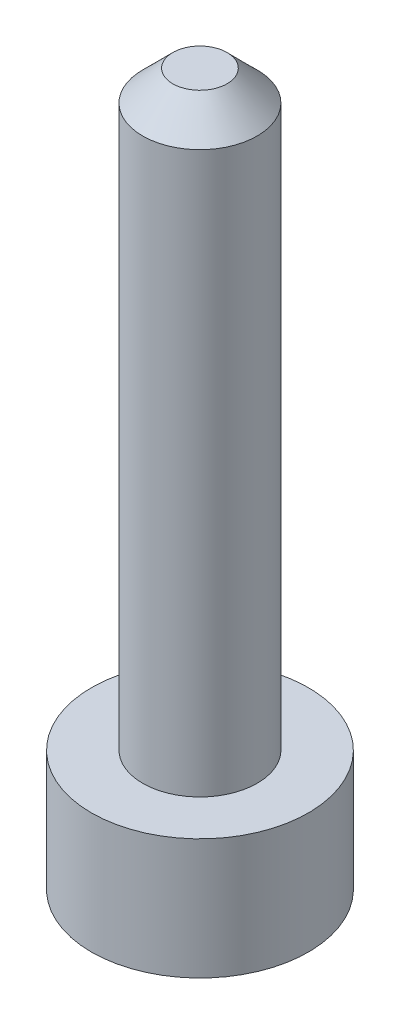
SolidWorks part; units mm, degrees
ref_plane "Front Plane" through (0, 0, 0) normal (0, 0, 1) x (1, 0, 0)
ref_plane "Top Plane" through (0, 0, 0) normal (0, 1, 0) x (1, 0, 0)
ref_plane "Right Plane" through (0, 0, 0) normal (1, 0, 0) x (0, 0, -1)
sketch "Sketch1" plane through (0, 0, 0) normal (0, 1, 0) x (1, 0, 0)
  line L1 (2.0785, 0) -> (1.0392, 1.8) construction
  line L2 (1.0392, 1.8) -> (-1.0392, 1.8) construction
  line L3 (-1.0392, 1.8) -> (-2.0785, 0) construction
  line L4 (-2.0785, 0) -> (-1.0392, -1.8) construction
  line L5 (-1.0392, -1.8) -> (1.0392, -1.8) construction
  line L6 (1.0392, -1.8) -> (2.0785, 0) construction
  circle A0 centre (0, 0) radius 1.8
  dimension "D1" = 3.6
extrude "Boss-Extrude1" add sketch "Sketch1" along normal blind 11.8
sketch "Sketch2" plane through (0, 11.8, 0) normal (0, 1, 0) x (1, 0, 0)
  circle A0 centre (0, 0) radius 0.95
  dimension "D1" = 1.9
extrude "Cut-Extrude1" cut sketch "Sketch2" against normal blind 9.8 flip side to cut
ref_axis "Axis1" through (0, 2, 0) along (0, 1, 0)
chamfer "Chamfer1" distance 0.5 angle 45 1 edges at (0, 11.8, 0.95)
sketch "Sketch5" plane through (0, 11.8, 0) normal (0, 1, 0) x (1, 0, 0)
  circle A0 centre (0, 0) radius 1.5
  dimension "D1" = 3
curve "Helix/Spiral1" pitch 0.7 height 8 turns 11.4286
ref_plane "Plane1" through (0, 11.8, 1.5) normal (-0.9973, -0.0741, 0) x (0, 0, 1)
sketch "Sketch8" plane through (0, 0, 0) normal (0, -1, 0) x (1, 0, 0)
  line L1 (1.1547, 0) -> (0.5774, 1)
  line L2 (0.5774, 1) -> (-0.5774, 1)
  line L3 (-0.5774, 1) -> (-1.1547, 0)
  line L4 (-1.1547, 0) -> (-0.5774, -1)
  line L5 (-0.5774, -1) -> (0.5774, -1)
  line L6 (0.5774, -1) -> (1.1547, 0)
  circle A0 centre (0, 0) radius 1 construction
  dimension "D1" = 2
extrude "Cut-Extrude2" cut sketch "Sketch8" against normal blind 1.5
